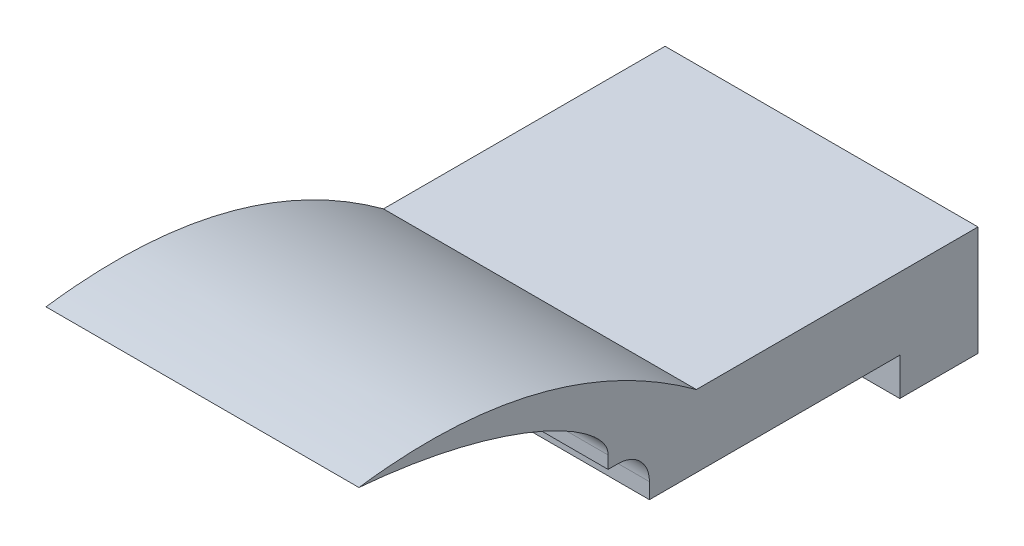
SolidWorks part; units mm, degrees
material "ABS"
ref_plane "Front Plane" through (0, 0, 0) normal (0, 0, 1) x (1, 0, 0)
ref_plane "Top Plane" through (0, 0, 0) normal (0, 1, 0) x (1, 0, 0)
ref_plane "Right Plane" through (0, 0, 0) normal (1, 0, 0) x (0, 0, -1)
curve "Curve1"
  spline degree 3 poles (0, 0.0012, 1.0003) (0, 0.0015, 0.9994) (0, 0.0028, 0.9958) (0, 0.0055, 0.9879) (0, 0.0099, 0.9747) (0, 0.0159, 0.9565) (0, 0.0233, 0.9333) (0, 0.0318, 0.9054) (0, 0.0411, 0.8731) (0, 0.051, 0.8366) (0, 0.0612, 0.7964) (0, 0.0713, 0.7528) (0, 0.0811, 0.7063) (0, 0.0903, 0.6574) (0, 0.0985, 0.6067) (0, 0.1057, 0.5546) (0, 0.1115, 0.5018) (0, 0.1158, 0.4488) (0, 0.1186, 0.3959) (0, 0.1189, 0.3436) (0, 0.1164, 0.2927) (0, 0.1112, 0.2442) (0, 0.1037, 0.1988) (0, 0.0942, 0.157) (0, 0.0831, 0.1194) (0, 0.0711, 0.0865) (0, 0.0584, 0.0585) (0, 0.0457, 0.0357) (0, 0.0334, 0.0184) (0, 0.0218, 0.0064) (0, 0.0108, -0.0005) (0, -0.0003, -0.0011) (0, -0.0092, 0.0055) (0, -0.0148, 0.017) (0, -0.0185, 0.0329) (0, -0.0204, 0.0533) (0, -0.0208, 0.0781) (0, -0.0198, 0.107) (0, -0.0176, 0.1398) (0, -0.0147, 0.176) (0, -0.0111, 0.2153) (0, -0.0074, 0.2574) (0, -0.0037, 0.3019) (0, -0.0005, 0.3484) (0, 0.002, 0.397) (0, 0.0037, 0.4471) (0, 0.0055, 0.4983) (0, 0.0069, 0.5496) (0, 0.0079, 0.6006) (0, 0.0085, 0.6505) (0, 0.0086, 0.699) (0, 0.0083, 0.7455) (0, 0.0076, 0.7894) (0, 0.0065, 0.8302) (0, 0.0053, 0.8675) (0, 0.0039, 0.9007) (0, 0.0027, 0.9296) (0, 0.0013, 0.9539) (0, 0.0006, 0.9727) (0, -0.0011, 0.9872) (0, 0, 0.9944) (0, -0.002, 0.9999) (0, -0.0005, 1) (0, 0, 1) knots 0 0 0 0 0.001372 0.005465 0.012235 0.021602 0.033461 0.047671 0.064081 0.082496 0.102719 0.124527 0.147676 0.171913 0.196978 0.222597 0.248497 0.274385 0.300041 0.32569 0.350525 0.37428 0.396711 0.417577 0.436654 0.453744 0.46868 0.481329 0.491631 0.499616 0.505546 0.510185 0.514824 0.520702 0.528516 0.538466 0.550543 0.564643 0.580638 0.598345 0.617584 0.638174 0.659922 0.682632 0.706121 0.730727 0.7557 0.780732 0.805564 0.829932 0.85357 0.876213 0.89761 0.917519 0.935698 0.951943 0.966047 0.97784 0.987174 0.993932 0.998018 0.999386 1 1 1 1
sketch "Sketch1" plane through (0, 0, 0) normal (1, 0, 0) x (0, 0, -1)
  line L1 (12.2165, 4.064) -> (12.2165, -1.016)
  line L3 (48.0533, 9.144) -> (48.0533, -35.306)
  line L4 (48.0533, -35.306) -> (29.0033, -35.306)
  line L5 (29.0033, -35.306) -> (29.0033, -1.016)
  line L6 (29.0033, -1.016) -> (12.2165, -1.016)
  line L8 (69.85, 0) -> (-69.85, 0) construction
  line L10 (0, 45.8699) -> (0, -45.8699) construction
  spline S0 degree 2 poles (-88.9, 43.18) (-12.9539, 53.7771) (48.0533, 9.144) knots 0 0 0 1 1 1
  spline S1 degree 3 poles (-88.9, 43.18) (-83.9463, 42.757) (-73.5905, 41.6218) (-58.3096, 39.1178) (-43.5398, 35.7782) (-30.2487, 31.895) (-18.5919, 27.6429) (-8.6949, 23.1943) (-0.6517, 18.7211) (5.5019, 14.3816) (9.7327, 10.2704) (11.8983, 6.8093) (12.2184, 4.6962) (12.2165, 4.064) knots 0.353791 0.353791 0.353791 0.353791 0.37428 0.396711 0.417577 0.436654 0.453744 0.46868 0.481329 0.491631 0.499616 0.505546 0.508115 0.508115 0.508115 0.508115
  dimension "D2" = 4.064
  dimension "D3" = 5.08
  dimension "D5" = 88.9
  dimension "D6" = 36.195
  dimension "D7" = 44.45
  dimension "D8" = 34.29
  dimension "D9" = 19.05
  dimension "D10" = 38.1
  dimension "D11" = 9.7768
  dimension "D12" = 48.0533
  dimension "D14" = 43.18
extrude "Boss-Extrude1" add sketch "Sketch1" along normal mid plane 127
sketch "Sketch2" plane through (0, 0, -48.0533) normal (0, 0, -1) x (-1, 0, 0)
  line L0 (-63.5, -11.176) -> (-31.75, -11.176) construction
  line L1 (-63.5, -35.306) -> (-63.5, 9.144) construction
  line L2 (-31.75, -11.176) -> (31.75, -11.176) construction
  line L3 (31.75, -11.176) -> (63.5, -11.176) construction
  line L4 (63.5, -35.306) -> (63.5, 9.144) construction
  line L5 (-63.5, 9.144) -> (63.5, 9.144) construction
  circle A0 centre (-31.75, -11.176) radius 3.302
  circle A1 centre (31.75, -11.176) radius 3.302
  dimension "D1" = 6.604
  dimension "D2" = 63.5
  dimension "D3" = 20.32
extrude "Cut-Extrude1" cut sketch "Sketch2" against normal through all both and the other way through all
sketch "Sketch3" plane through (0, 0, -48.0533) normal (0, 0, -1) x (-1, 0, 0)
  line L4 (63.5, -35.306) -> (63.5, 9.144)
  line L5 (63.5, 9.144) -> (-63.5, 9.144)
  line L6 (-63.5, 9.144) -> (-63.5, -35.306)
  line L7 (-63.5, -35.306) -> (63.5, -35.306)
  line L8 (63.5, -35.306) -> (63.5, 9.144)
  line L9 (63.5, 9.144) -> (-63.5, 9.144)
  line L10 (-63.5, 9.144) -> (-63.5, -35.306)
  line L11 (-63.5, -35.306) -> (63.5, -35.306)
  circle A0 centre (-31.75, -11.176) radius 3.302 construction
  circle A1 centre (-31.75, -11.176) radius 3.302
  circle A2 centre (31.75, -11.176) radius 3.302 construction
  circle A3 centre (31.75, -11.176) radius 3.302
  dimension "D1" = 0
extrude "Boss-Extrude2" add sketch "Sketch3" along normal blind 114.3
sketch "Sketch4" plane through (-63.5, 0, 0) normal (-1, 0, 0) x (0, 0, 1)
  line L1 (-29.0033, -35.306) -> (-130.6033, -35.306)
  line L2 (-29.0033, -35.306) -> (-29.0033, -20.066)
  line L3 (-29.0033, -20.066) -> (-130.6033, -20.066)
  line L4 (-130.6033, -35.306) -> (-130.6033, -20.066)
  dimension "D1" = 101.6
  dimension "D2" = 15.24
extrude "Cut-Extrude2" cut sketch "Sketch4" against normal through all
fillet "Fillet1" radius 12.7 1 edges at (0, -1.016, -29.0033)
